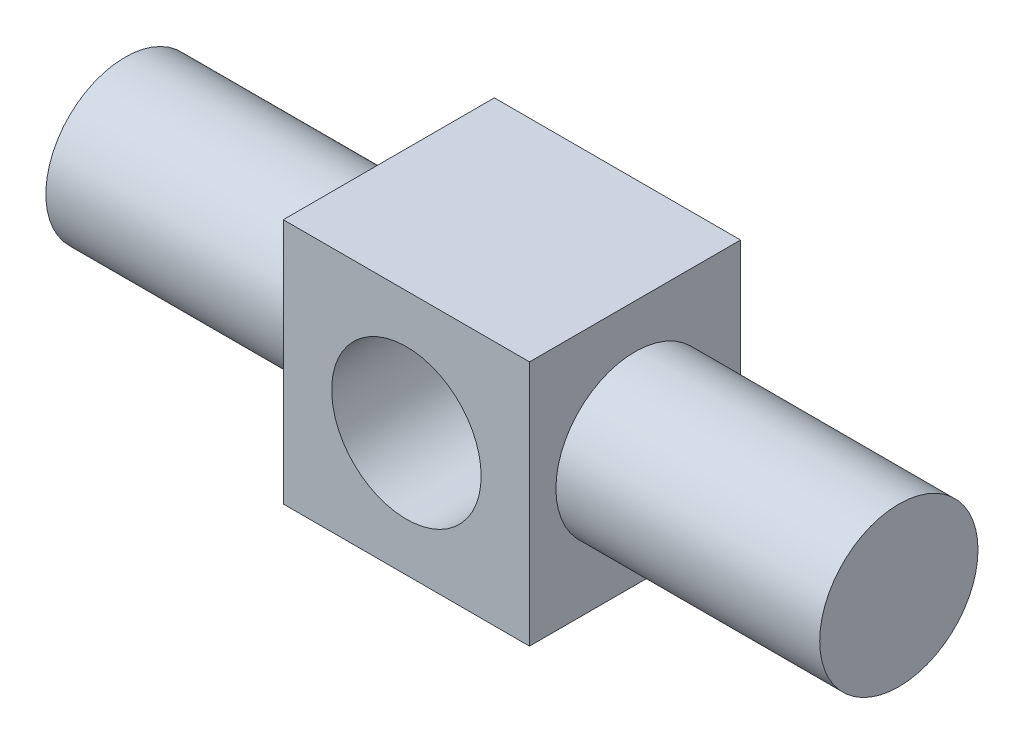
SolidWorks part; units mm, degrees
ref_plane "前视基准面" through (0, 0, 0) normal (0, 0, 1) x (1, 0, 0)
ref_plane "上视基准面" through (0, 0, 0) normal (0, 1, 0) x (1, 0, 0)
ref_plane "右视基准面" through (0, 0, 0) normal (1, 0, 0) x (0, 0, -1)
sketch "草图1" plane through (0, 0, 0) normal (0, 0, 1) x (1, 0, 0)
  line L1 (-7, -7) -> (7, -7)
  line L2 (-7, -7) -> (-7, 7)
  line L3 (-7, 7) -> (7, 7)
  line L4 (7, -7) -> (7, 7)
  line L5 (-7, -7) -> (7, 7) construction
  line L6 (-7, 7) -> (7, -7) construction
  point P0 (0, 0)
  dimension "D1" = 14
  dimension "D2" = 14
extrude "凸台-拉伸1" add sketch "草图1" along normal mid plane 12
sketch "草图2" plane through (7, 0, 0) normal (1, 0, 0) x (0, 0, -1)
  circle A0 centre (0, 0) radius 4.5
  dimension "D1" = 9
extrude "凸台-拉伸2" add sketch "草图2" along normal blind 15
mirror "镜向1" about plane through (0, 0, 0) normal (1, 0, 0) of "凸台-拉伸2"
sketch "草图3" plane through (0, 0, 6) normal (0, 0, 1) x (1, 0, 0)
  point P0 (0, 0)
hole_wizard "M10 螺纹孔1" positions "3D草图1" profile "草图4" tap size "M10" standard "GB" end condition through all
sketch3d "3D草图1"
  point P0 (0, 0, 6)
sketch "草图4" plane through (0, 0, 6) normal (1, 0, 0) x (0, -1, 0)
  line L0 (0, 0) -> (0, 12)
  line L1 (0, 12) -> (4.25, 12)
  line L2 (4.25, 12) -> (4.25, 0)
  line L5 (4.25, 0) -> (0, 0)
  line L11 (0, -6.35) -> (0, 107.95) construction
  dimension "通孔螺纹孔钻头直径" = 8.5
  dimension "通孔螺纹孔钻头深度" = 12
cosmetic thread "孔螺蚊线1" parameters "D2"=10
